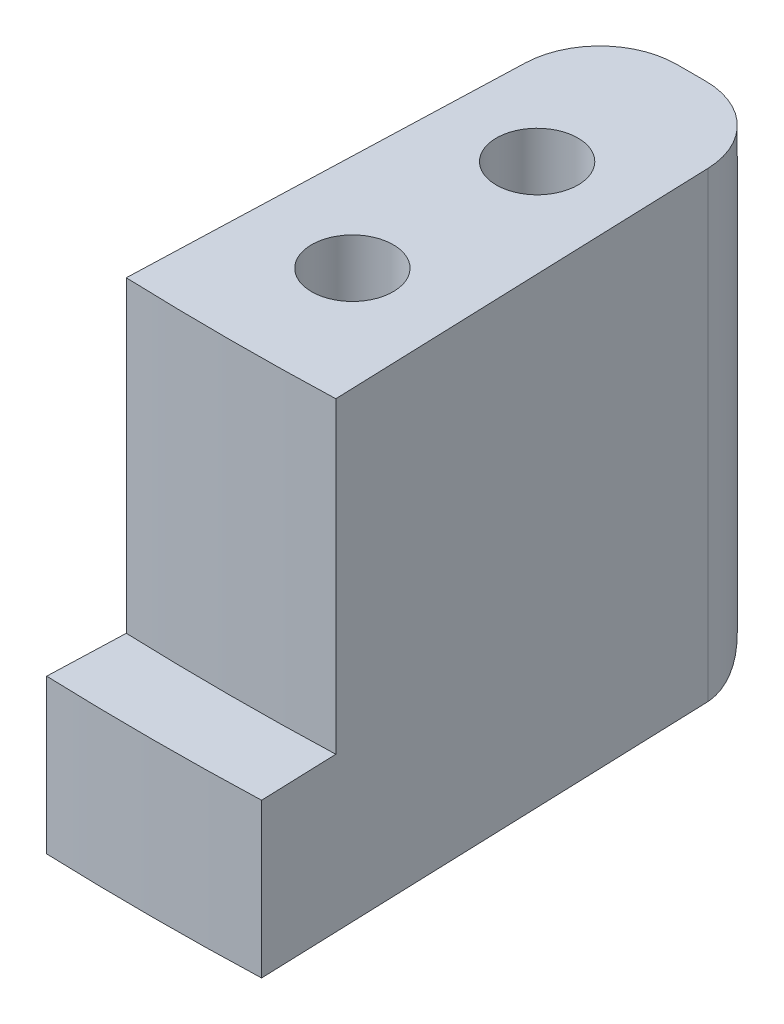
SolidWorks part; units mm, degrees
ref_plane "前视基准面" through (0, 0, 0) normal (0, 0, 1) x (1, 0, 0)
ref_plane "上视基准面" through (0, 0, 0) normal (0, 1, 0) x (1, 0, 0)
ref_plane "右视基准面" through (0, 0, 0) normal (1, 0, 0) x (0, 0, -1)
ref_axis "顶盖中心轴" through (0, -55, 0) along (0, 1, 0)
sketch "草图1" plane through (0, 0, 0) normal (0, 1, 0) x (1, 0, 0)
  line L0 (-5.9355, -169.97) -> (-6.0728, -173.9021) construction
  line L1 (0, 0) -> (0, -125.794) construction
  line L3 (-5.7619, -165) -> (5.7619, -165)
  line L4 (-5.7619, -165) -> (-6.9799, -199.8782)
  line L5 (5.7619, -165) -> (6.9799, -199.8782)
  arc A0 (-6.8054, -194.8812) -> (6.8054, -194.8812) centre (0, 0) ccw
  arc A1 (-6.9799, -199.8782) -> (6.9799, -199.8782) centre (0, 0) ccw
  dimension "D1" = 2
  dimension "D2" = 195
  dimension "D4" = 200
  dimension "D3" = 165
extrude "主体" add sketch "草图1" along normal blind 30 contours L4 A0 L5 L3 region at (0, 0, 180.3958)
extrude "插销" add sketch "草图1<3>" along normal blind 10 contours L4 A1 L5 A0 region at (0, 0, 197.4704)
sketch "草图1<3>" plane through (0, 0, 0) normal (0, 1, 0) x (1, 0, 0) same geometry as "草图1"
ref_plane "对称面" through (0, 0, 0) normal (1, 0, 0) x (0, 0, -1)
fillet "圆角1" radius 5 3 edges at (-5.7619, 15, 165) (5.7619, 15, 165) (0, 0, 165)
hole_wizard "M5 间隙孔1" positions "草图4" profile "草图5" hole size "M5" standard "ISO" end condition up to next
sketch "草图4" plane through (0, 30, 0) normal (0, 1, 0) x (1, 0, 0)
  line L0 (0, -13.75) -> (0, 13.75) construction
  point P0 (0, -187)
  point P2 (0, -175)
  point P5 (0, 0)
  point P8 (0, 0)
  point P10 (0, 0)
  point P11 (0, 0)
  dimension "D1" = 175
  dimension "D2" = 187
sketch "草图5" plane through (0, 30, 187) normal (1, 0, 0) x (0, 0, 1)
  line L0 (0, 0) -> (0, 30)
  line L1 (0, 30) -> (2.65, 30)
  line L2 (2.65, 30) -> (2.65, 0)
  line L5 (2.65, 0) -> (0, 0)
  line L11 (0, -6.35) -> (0, 107.95) construction
  dimension "通孔孔直径" = 5.3
  dimension "通孔孔深度" = 30
sketch "草图6" plane through (0, 0, 0) normal (0, -1, 0) x (1, 0, 0)
  line L1 (-4.6765, 175) -> (-2.3383, 170.95)
  line L2 (-2.3383, 170.95) -> (2.3383, 170.95)
  line L3 (2.3383, 170.95) -> (4.6765, 175)
  line L4 (4.6765, 175) -> (2.3383, 179.05)
  line L5 (2.3383, 179.05) -> (-2.3383, 179.05)
  line L6 (-2.3383, 179.05) -> (-4.6765, 175)
  line L7 (-4.6765, 187) -> (-2.3383, 182.95)
  line L8 (-2.3383, 182.95) -> (2.3383, 182.95)
  line L9 (2.3383, 182.95) -> (4.6765, 187)
  line L10 (4.6765, 187) -> (2.3383, 191.05)
  line L11 (2.3383, 191.05) -> (-2.3383, 191.05)
  line L12 (-2.3383, 191.05) -> (-4.6765, 187)
  circle A0 centre (0, 175) radius 4.05 construction
  circle A1 centre (0, 187) radius 4.05 construction
  point P9 (0, 0)
  point P17 (0, 0)
  point P18 (0, 0)
  point P20 (0, 0)
extrude "切除-拉伸1" cut sketch "草图6" against normal blind 5
